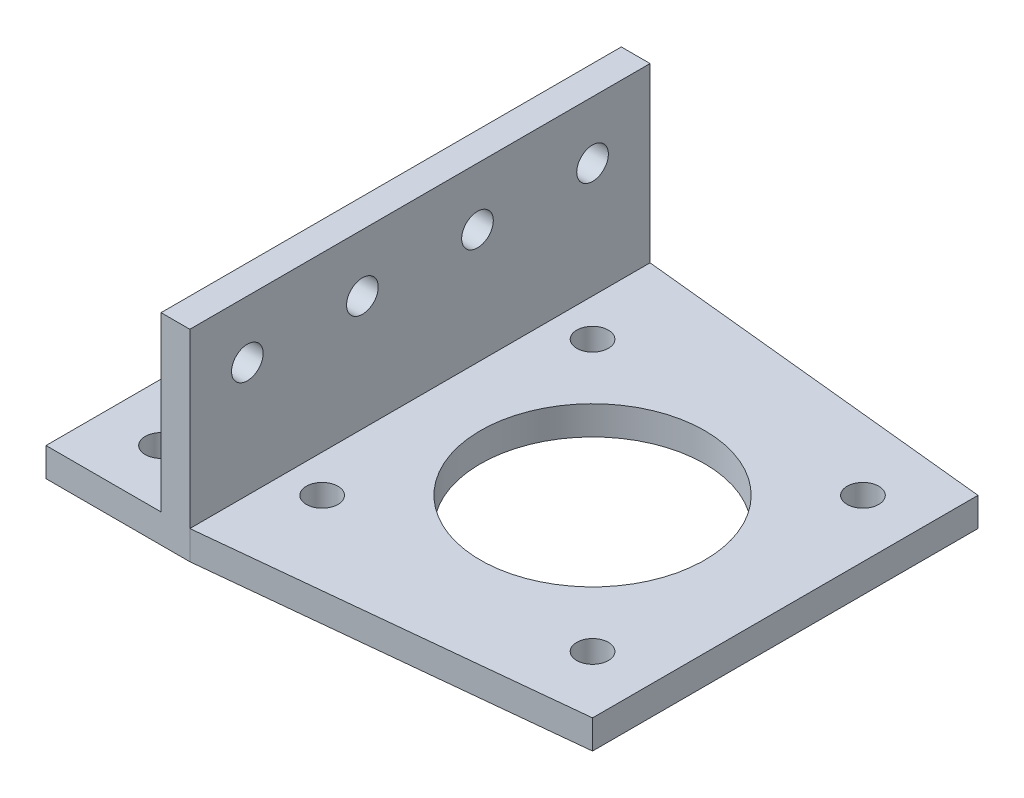
SolidWorks part; units mm, degrees
ref_plane "Plan de face" through (0, 0, 0) normal (0, 0, 1) x (1, 0, 0)
ref_plane "Plan de dessus" through (0, 0, 0) normal (0, 1, 0) x (1, 0, 0)
ref_plane "Plan de droite" through (0, 0, 0) normal (1, 0, 0) x (0, 0, -1)
sketch "Esquisse1" plane through (0, 0, 0) normal (0, 0, 1) x (1, 0, 0)
  line L0 (-4.6419, 0) -> (-4.6419, 35)
  line L1 (-4.6419, 35) -> (-9.6419, 35)
  line L2 (-9.6419, 35) -> (-9.6419, 5)
  line L3 (-9.6419, 5) -> (-29.6419, 5)
  line L4 (-29.6419, 5) -> (-29.6419, 0)
  line L5 (-29.6419, 0) -> (-4.6419, 0)
  dimension "D1" = 20
  dimension "D2" = 5
  dimension "D3" = 30
extrude "Boss.-Extru.1" add sketch "Esquisse1" along normal blind 80
sketch "Esquisse2" plane through (-9.6419, 0, 0) normal (-1, 0, 0) x (0, 0, 1)
  line L0 (0, 35) -> (0, 5) construction
  line L1 (80, 35) -> (80, 5) construction
  line L2 (80, 35) -> (0, 35) construction
  circle A0 centre (10, 25) radius 2.75
  circle A1 centre (50, 25) radius 2.75
  circle A2 centre (70, 25) radius 2.75
  circle A3 centre (30, 25) radius 2.75
  dimension "D1" = 10
  dimension "D5" = 5.5
  dimension "D2" = 10
  dimension "D3" = 20
  dimension "D4" = 20
  dimension "D6" = 10
extrude "Enlèv. mat.-Extru.1" cut sketch "Esquisse2" against normal up to next
sketch "Esquisse3" plane through (0, 5, 0) normal (0, 1, 0) x (1, 0, 0)
  line L0 (-9.6419, -7.25) -> (-9.6419, -12.75) construction
  line L1 (-9.6419, -27.25) -> (-9.6419, -32.75) construction
  line L2 (-9.6419, -47.25) -> (-9.6419, -52.75) construction
  line L3 (-9.6419, -67.25) -> (-9.6419, -72.75) construction
  line L4 (-9.6419, -7.25) -> (-9.6419, -12.75) construction
  line L5 (-9.6419, -27.25) -> (-9.6419, -32.75) construction
  line L6 (-9.6419, -47.25) -> (-9.6419, -52.75) construction
  line L7 (-9.6419, -67.25) -> (-9.6419, -72.75) construction
  line L8 (-9.6419, 0) -> (-29.6419, 0) construction
  circle A0 centre (-19.6419, -10) radius 2.75
  circle A1 centre (-19.6419, -30) radius 2.75
  circle A2 centre (-19.6419, -50) radius 2.75
  circle A3 centre (-19.6419, -70) radius 2.75
  point P17 (-9.6419, -70)
  point P19 (-9.6419, -50)
  point P21 (-9.6419, -30)
  point P23 (-9.6419, -10)
  point P27 (-19.6419, 0)
  dimension "D1" = 5.5
extrude "Enlèv. mat.-Extru.2" cut sketch "Esquisse3" against normal up to next
sketch "Esquisse5" plane through (0, 0, 0) normal (0, -1, 0) x (1, 0, 0)
  line L0 (58.8581, 73.5) -> (-4.6419, 80)
  line L1 (-4.6419, 0) -> (58.8581, 6.5)
  line L2 (-4.6419, 0) -> (-4.6419, 80)
  line L4 (58.8581, 6.5) -> (58.8581, 73.5)
  line L5 (48.8581, 16.5) -> (48.8581, 63.5) construction
  line L6 (48.8581, 16.5) -> (1.8581, 16.5) construction
  line L7 (48.8581, 16.5) -> (58.8581, 16.5) construction
  line L8 (48.8581, 16.5) -> (48.8581, 6.5) construction
  line L9 (48.8581, 63.5) -> (58.8581, 63.5) construction
  line L10 (48.8581, 63.5) -> (48.8581, 73.5) construction
  circle A0 centre (25.3581, 40) radius 19.5
  circle A1 centre (48.8581, 16.5) radius 2.75
  circle A2 centre (48.8581, 63.5) radius 2.75
  circle A3 centre (1.8581, 63.5) radius 2.75
  circle A4 centre (1.8581, 16.5) radius 2.75
  point P16 (48.8581, 40)
  point P18 (25.3581, 16.5)
  point P24 (-4.6419, 40)
  line M6 (-4.6419, 0) -> (-4.6419, 80)
  dimension "D3" = 39
  dimension "D4" = 5.5
  dimension "D1" = 30
  dimension "D2" = 10
  dimension "D5" = 47
extrude "Boss.-Extru.2" add sketch "Esquisse5" against normal blind 5 contours A4 L1 L4 L0 A3 A2 A1 A0 M6 region at (57.8368, 0, 40)
